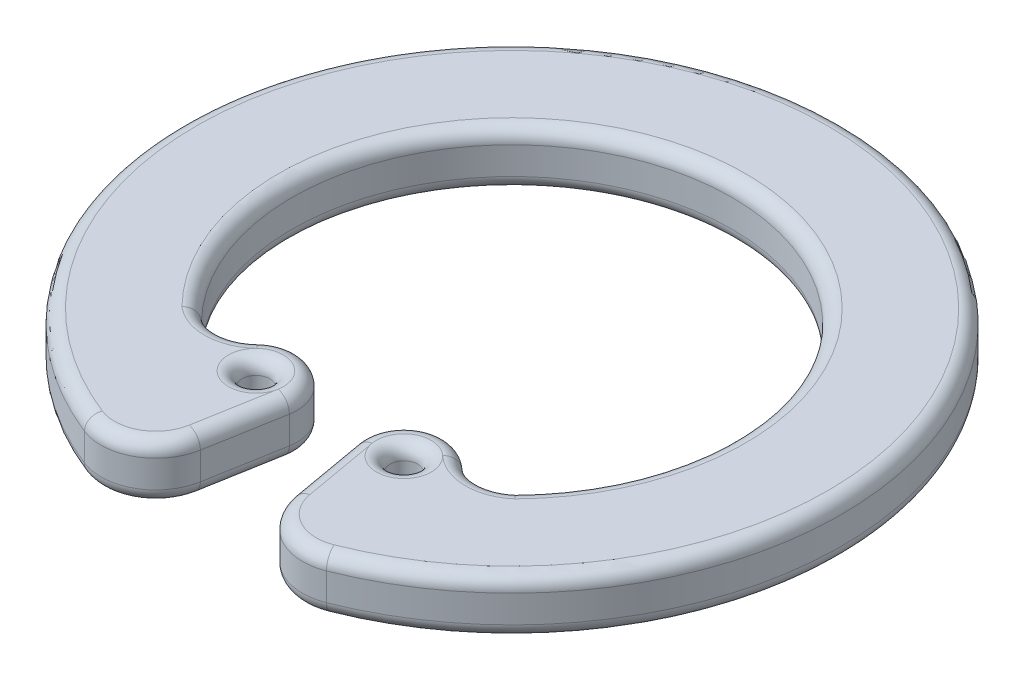
SolidWorks part; units mm, degrees
material "Teak"
ref_plane "Plano frontal" through (0, 0, 0) normal (0, 0, 1) x (1, 0, 0)
ref_plane "Plano superior" through (0, 0, 0) normal (0, 1, 0) x (1, 0, 0)
ref_plane "Plano direito" through (0, 0, 0) normal (1, 0, 0) x (0, 0, -1)
sketch "Sketch1" plane through (0, 0, 0) normal (0, 1, 0) x (1, 0, 0)
  line L0 (0, 0) -> (0, -12) construction
  line L1 (1.2155, -6.8937) -> (1.7014, -9.6491)
  line L2 (-1.2155, -6.8937) -> (-1.7014, -9.6491)
  arc A0 (5.722, -5.5909) -> (-5.722, -5.5909) centre (0, 0) ccw
  arc A1 (4.4052, -11.1622) -> (-4.4052, -11.1622) centre (0, 0) ccw
  arc A2 (1.2155, -6.8937) -> (3.721, -5.5411) centre (2.6927, -6.6332) cw
  arc A3 (3.721, -5.5411) -> (5.722, -5.5909) centre (4.7493, -4.4491) ccw
  arc A4 (1.7014, -9.6491) -> (4.4052, -11.1622) centre (3.671, -9.3018) ccw
  circle A5 centre (2.6927, -6.6332) radius 0.5
  arc A6 (-1.7014, -9.6491) -> (-4.4052, -11.1622) centre (-3.671, -9.3018) cw
  circle A7 centre (-2.6927, -6.6332) radius 0.5
  arc A8 (-1.2155, -6.8937) -> (-3.721, -5.5411) centre (-2.6927, -6.6332) ccw
  arc A9 (-3.721, -5.5411) -> (-5.722, -5.5909) centre (-4.7493, -4.4491) cw
  point P17 (2.0838, -11.8177)
  dimension "D1" = 16
  dimension "D2" = 24
  dimension "D5" = 1.5
  dimension "D6" = 1.5
  dimension "D7" = 2
  dimension "D8" = 1
  dimension "D3" = 5
  dimension "D4" = 10
extrude "Boss-Extrude1" add sketch "Sketch1" along normal mid plane 2
fillet "Fillet1" radius 0.5 24 edges at (-2.6927, 1, 6.1332) (1.4585, 1, 8.2714) (1.9802, 1, 5.3132) (4.712, 1, 5.9486) (0, 1, -8) (-4.712, 1, 5.9486) (-1.9802, 1, 5.3132) (-1.4585, 1, 8.2714) (-2.6943, 1, 11.0471) (0, 1, -12) (2.6943, 1, 11.0471) (2.6927, 1, 7.1332) (-2.6927, -1, 6.1332) (2.6927, -1, 7.1332) (0, -1, -12) (-2.6943, -1, 11.0471) (-1.4585, -1, 8.2714) (-1.9802, -1, 5.3132) (-4.712, -1, 5.9486) (0, -1, -8) (4.712, -1, 5.9486) (1.9802, -1, 5.3132) (1.4585, -1, 8.2714) (2.6943, -1, 11.0471)
